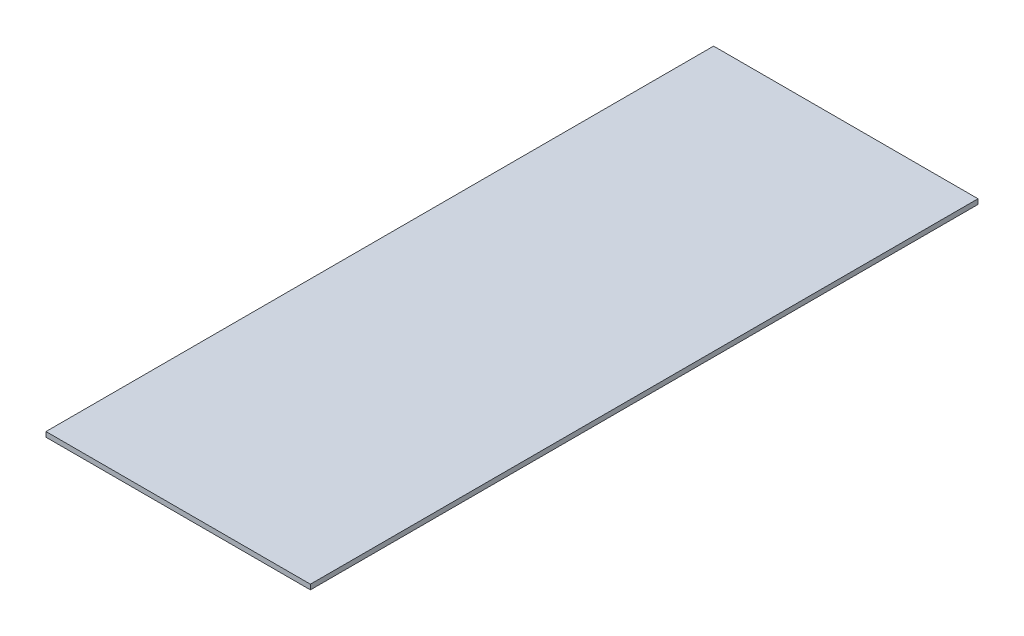
SolidWorks part; units mm, degrees
material "Hexcel AS4C (3000 Filaments)"
ref_plane "Front Plane" through (0, 0, 0) normal (0, 0, 1) x (1, 0, 0)
ref_plane "Top Plane" through (0, 0, 0) normal (0, 1, 0) x (1, 0, 0)
ref_plane "Right Plane" through (0, 0, 0) normal (1, 0, 0) x (0, 0, -1)
sketch "Sketch1" plane through (0, 0, 0.0479) normal (0, 1, 0) x (1, 0, 0)
  line L1 (-32.2125, 199.9208) -> (127.7875, 199.9208)
  line L2 (-32.2125, 199.9208) -> (-32.2125, -204.0792)
  line L3 (-32.2125, -204.0792) -> (127.7875, -204.0792)
  line L4 (127.7875, 199.9208) -> (127.7875, -204.0792)
  dimension "D1" = 160
  dimension "D2" = 404
extrude "Boss-Extrude1" add sketch "Sketch1" along normal blind 3
ref_plane "Plane1" through (0, 3, 0) normal (0, 1, 0) x (1, 0, 0)
sketch "Sketch2" plane through (0, 3, 0) normal (0, 1, 0) x (1, 0, 0)
  line L0 (-32.2125, -204.1271) -> (47.7875, -204.1271)
  line L1 (-32.2125, -204.1271) -> (127.7875, -204.1271) construction
  line L2 (47.7875, -204.1271) -> (47.7875, 199.8729)
  line L3 (127.7875, 199.8729) -> (-32.2125, 199.8729) construction
  line L5 (32.7875, 202) -> (62.7875, 202)
  line L6 (32.7875, 202) -> (32.7875, -202)
  line L7 (32.7875, -202) -> (62.7875, -202)
  line L8 (62.7875, 202) -> (62.7875, -202)
  line L9 (32.7875, 202) -> (62.7875, -202) construction
  line L10 (32.7875, -202) -> (62.7875, 202) construction
  point P5 (47.7875, 0)
  dimension "D1" = 30
  dimension "D2" = 404
